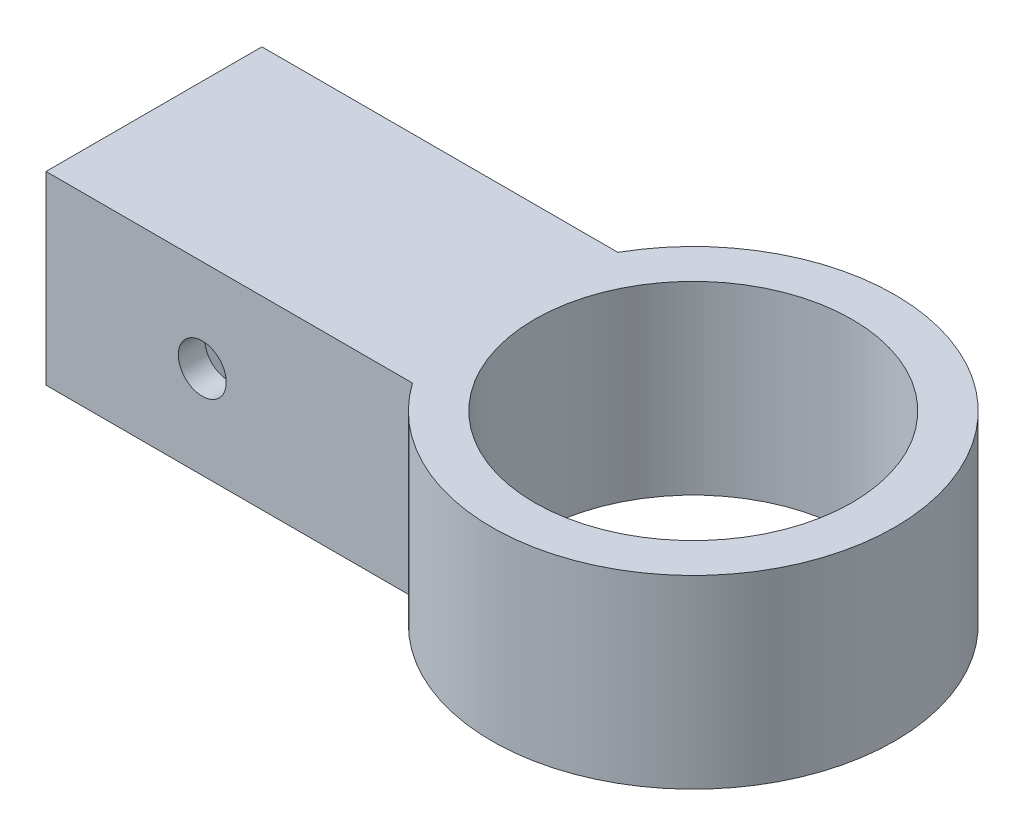
SolidWorks part; units mm, degrees
ref_plane "Plano frontal" through (0, 0, 0) normal (0, 0, 1) x (1, 0, 0)
ref_plane "Plano superior" through (0, 0, 0) normal (0, 1, 0) x (1, 0, 0)
ref_plane "Plano direito" through (0, 0, 0) normal (1, 0, 0) x (0, 0, -1)
sketch "Esboço2" plane through (0, 0, 0) normal (0, 1, 0) x (1, 0, 0)
  line L1 (-55, 0) -> (55, 0) construction
  line L4 (-12.2973, 7) -> (-37.2973, 7)
  line L5 (-37.2973, -8.161) -> (-37.2973, 7)
  line L8 (-37.2973, -8.161) -> (-11.5594, -8.161)
  circle A0 centre (0, 0) radius 11.15
  arc A1 (-11.5594, -8.161) -> (-12.2973, 7) centre (0, 0) ccw
  point P2 (0, 0)
  point P10 (-23.4373, -8.161)
  dimension "D1" = 22.3
  dimension "D3" = 7
  dimension "D2" = 3
  dimension "D4" = 25
extrude "Ressalto-extrusão1" add sketch "Esboço2" along normal blind 13
sketch "Esboço3" plane through (-37.2973, 0, 0) normal (-1, 0, 0) x (0, 0, 1)
  line L0 (0, -55) -> (0, 55) construction
  line L1 (3.5, 3) -> (-3.5, 3)
  line L2 (3.5, 3) -> (3.5, 10)
  line L3 (3.5, 10) -> (-3.5, 10)
  line L4 (-3.5, 3) -> (-3.5, 10)
  line L5 (3.5, 3) -> (-3.5, 10) construction
  line L6 (3.5, 10) -> (-3.5, 3) construction
  point P0 (0, 6.5)
extrude "Corte-extrusão1" cut sketch "Esboço3" against normal blind 26
sketch "Esboço7" plane through (0, 0, 3.5) normal (0, 0, -1) x (-1, 0, 0)
  line L0 (26.3212, 13) -> (26.3212, 0) construction
  line L1 (22.6262, 6.5) -> (24.4737, 3.3)
  line L2 (24.4737, 3.3) -> (28.1688, 3.3)
  line L3 (28.1688, 3.3) -> (30.0163, 6.5)
  line L4 (30.0163, 6.5) -> (28.1688, 9.7)
  line L5 (28.1688, 9.7) -> (24.4737, 9.7)
  line L6 (24.4737, 9.7) -> (22.6262, 6.5)
  line L7 (37.2973, 13) -> (11.5594, 13) construction
  line L8 (37.2973, 0) -> (11.5594, 0) construction
  circle A0 centre (26.3212, 6.5) radius 3.2 construction
  point P1 (26.3212, -8.374)
  point P15 (26.3212, 6.5)
extrude "Corte-extrusão2" cut sketch "Esboço7" against normal blind 2.8
sketch "Esboço10" plane through (0, 0, 6.3) normal (0, 0, -1) x (-1, 0, 0)
  line L0 (24.4737, 9.7) -> (28.1688, 3.3) construction
  circle A0 centre (26.3212, 6.5) radius 1.6837
  point P2 (25.8323, 5.8744)
  point P7 (26.3212, 6.5)
extrude "Corte-extrusão3" cut sketch "Esboço10" against normal blind 2.8
